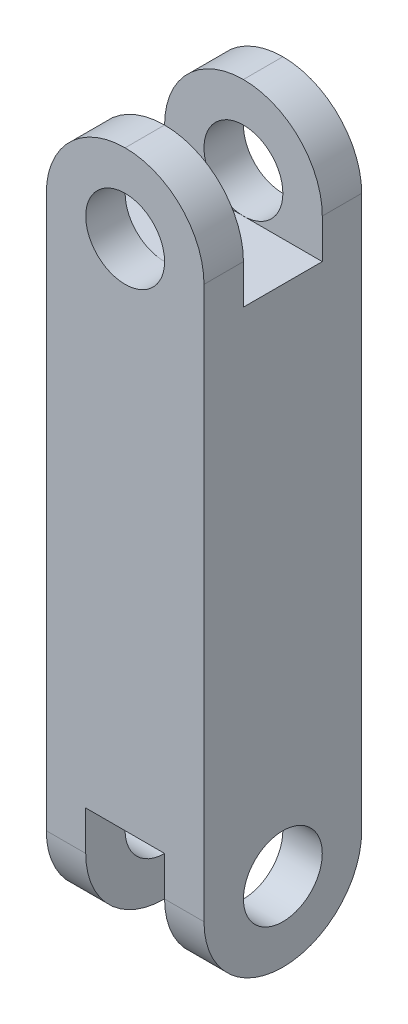
SolidWorks part; units mm, degrees
ref_plane "Front Plane" through (0, 0, 0) normal (0, 0, 1) x (1, 0, 0)
ref_plane "Top Plane" through (0, 0, 0) normal (0, 1, 0) x (1, 0, 0)
ref_plane "Right Plane" through (0, 0, 0) normal (1, 0, 0) x (0, 0, -1)
sketch "Sketch2" plane through (0, 0, 0) normal (0, 1, 0) x (1, 0, 0)
  line L1 (-50.8, -50.8) -> (50.8, -50.8)
  line L2 (-50.8, -50.8) -> (-50.8, 50.8)
  line L3 (-50.8, 50.8) -> (50.8, 50.8)
  line L4 (50.8, -50.8) -> (50.8, 50.8)
  line L5 (-50.8, -50.8) -> (50.8, 50.8) construction
  line L6 (-50.8, 50.8) -> (50.8, -50.8) construction
  point P0 (0, 0)
  dimension "D1" = 101.6
  dimension "D2" = 101.6
extrude "Boss-Extrude1" add sketch "Sketch2" along normal blind 457.2
sketch "Sketch3" plane through (0, 0, 0) normal (0, 0, 1) x (1, 0, 0)
  line L0 (-50.8, 0) -> (50.8, 0) construction
  line L1 (-25.4, 0) -> (25.4, 0)
  line L2 (-25.4, 0) -> (-25.4, 76.2)
  line L3 (-25.4, 76.2) -> (25.4, 76.2)
  line L4 (25.4, 0) -> (25.4, 76.2)
  line L5 (-50.8, 457.2) -> (-50.8, 0) construction
  line L6 (-50.8, 457.2) -> (50.8, 457.2) construction
  circle A0 centre (0, 406.4) radius 25.4
  dimension "D4" = 50.8
  dimension "D1" = 50.8
  dimension "D2" = 76.2
  dimension "D3" = 25.4
  dimension "D5" = 50.8
extrude "Cut-Extrude1" cut sketch "Sketch3" against normal through all both and the other way through all
fillet "Fillet1" radius 50.8 6 edges at (-38.1, 0, -50.8) (-38.1, 0, 50.8) (38.1, 0, -50.8) (38.1, 0, 50.8) (-50.8, 457.2, 0) (50.8, 457.2, 0)
sketch "Sketch4" plane through (50.8, 0, 0) normal (1, 0, 0) x (0, 0, -1)
  line L1 (-25.4, 381) -> (25.4, 381)
  line L2 (-25.4, 381) -> (-25.4, 457.2)
  line L3 (-25.4, 457.2) -> (25.4, 457.2)
  line L4 (25.4, 381) -> (25.4, 457.2)
  line L6 (-50.8, 457.2) -> (-50.8, 406.4) construction
  circle A0 centre (0, 50.8) radius 25.4
  dimension "D1" = 50.8
  dimension "D2" = 50.8
  dimension "D3" = 50.8
  dimension "D4" = 25.4
  dimension "D5" = 76.2
extrude "Cut-Extrude2" cut sketch "Sketch4" against normal through all both
